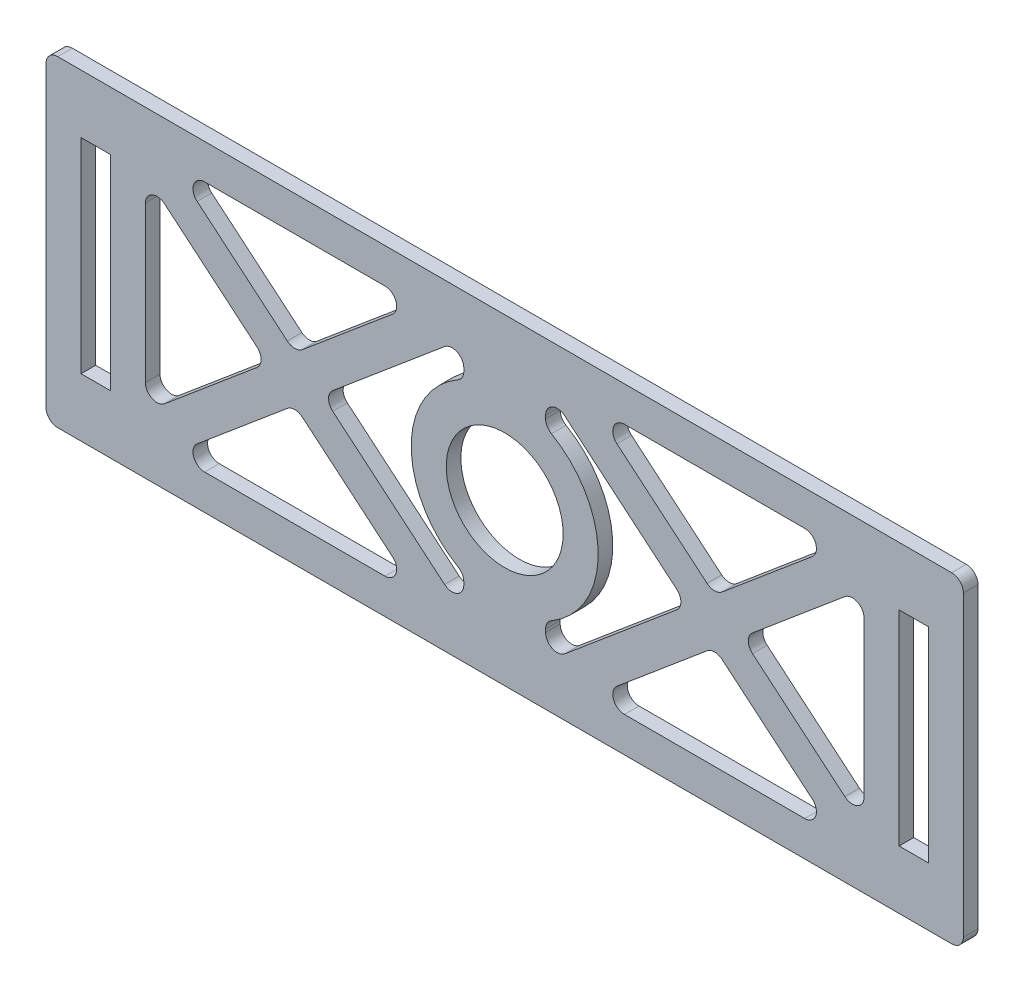
SolidWorks part; units mm, degrees
ref_plane "Front Plane" through (0, 0, 0) normal (0, 0, 1) x (1, 0, 0)
ref_plane "Top Plane" through (0, 0, 0) normal (0, 1, 0) x (1, 0, 0)
ref_plane "Right Plane" through (0, 0, 0) normal (1, 0, 0) x (0, 0, -1)
sketch "Sketch1" plane through (0, 0, 0) normal (0, 0, 1) x (1, 0, 0)
  line L0 (88.9, -28.575) -> (88.9, -73.025) construction
  line L1 (-99.695, -15.875) -> (99.695, -15.875)
  line L2 (-99.695, -15.875) -> (-99.695, -85.725)
  line L3 (-99.695, -85.725) -> (99.695, -85.725)
  line L4 (99.695, -15.875) -> (99.695, -85.725)
  line L5 (85.725, -28.575) -> (92.075, -28.575)
  line L6 (85.725, -28.575) -> (85.725, -73.025)
  line L7 (85.725, -73.025) -> (92.075, -73.025)
  line L8 (92.075, -28.575) -> (92.075, -73.025)
  line L9 (8.89, -23.495) -> (8.89, -24.9079)
  line L10 (8.89, -78.105) -> (78.105, -78.105)
  line L11 (78.105, -78.105) -> (78.105, -23.495)
  line L12 (78.105, -23.495) -> (8.89, -23.495)
  line L13 (8.89, -78.105) -> (8.89, -76.6921)
  line L14 (8.89, -24.9079) -> (72.1834, -78.105)
  line L15 (78.105, -78.105) -> (13.1305, -23.495)
  line L16 (78.105, -73.128) -> (19.0521, -23.495)
  line L17 (27.0702, -40.1881) -> (31.973, -34.3548) construction
  line L18 (2.2061, -50.8) -> (31.6359, -50.8) construction
  line L19 (78.105, -28.472) -> (19.0521, -78.105)
  line L20 (8.89, -76.6921) -> (72.1834, -23.495)
  line L21 (8.89, -32.5279) -> (8.89, -24.9079)
  line L22 (8.89, -76.6921) -> (8.89, -69.0721)
  circle A0 centre (0, -50.8) radius 12.7
  arc A1 (8.89, -24.9079) -> (8.89, -76.6921) centre (0, -50.8) cw
  arc A2 (8.89, -32.5279) -> (8.89, -69.0721) centre (0, -50.8) cw
  point P2 (0, -50.8)
  point P11 (85.725, -50.8)
  point P14 (0, -15.875)
  point P28 (29.5216, -37.2714)
  point P33 (78.105, -50.8)
  dimension "D1" = 25.4
  dimension "D2" = 44.45
  dimension "D3" = 6.35
  dimension "D4" = 88.9
  dimension "D5" = 12.7
  dimension "D6" = 7.62
  dimension "D7" = 12.7
  dimension "D9" = 7.62
  dimension "D12" = 7.62
  dimension "D13" = 50.8
  dimension "D8" = 7.62
  dimension "D10" = 8.89
  dimension "D11" = 7.62
  dimension "D14" = 7.62
extrude "Boss-Extrude1" add sketch "Sketch1" along normal mid plane 3.175 contours L4 L1 L2 L3 A1 L14 L9 L12 L11 L10 L13 L20 A0 L5 L8 L7 L6 | L14 L19 L10 | L20 A1 L13 L10 L19 L14 | L20 L14 L19 | L20 L19 L16 | L19 L14 L10 | L16 L19 L11 | L11 L19 L16 | L20 L16 L19 L11 L12 | L16 L20 L12 | L20 L16 L12 | L9 A1 L14 L20 | L14 A1 L20 | A1 L20 | A1 L14 | L21 A2 L22 L20 A1 L14 region at (-19.201, -50.8, 0) region at (27.442, -37.7533, 0) region at (16.9069, -30.6844, 0) region at (16.0795, -31.6688, 0) region at (30.0753, -35.2921, 0) region at (30.8144, -50.8, 0) region at (45.6178, -30.9377, 0) region at (47.0982, -49.5558, 0) region at (44.1374, -52.0442, 0) region at (28.8113, -65.1265, 0) region at (16.9069, -70.9156, 0) region at (62.6146, -36.5144, 0) region at (64.069, -63.8632, 0) region at (61.1603, -66.3079, 0) region at (45.6178, -70.6623, 0) region at (69.2498, -50.8, 0)
extrude "Cut-Extrude1" cut sketch "Sketch1<3>" against normal mid plane 6.35 contours L14 A1 L20 | L16 L20 L12 | L11 L19 L16 | L14 L19 L10 | L8 L5 L6 L7 | L21 A2 L22 L20 A1 L14 region at (88.9, -50.8, 0) region at (16.0795, -31.6688, 0) region at (30.8144, -50.8, 0) region at (45.6178, -30.9377, 0) region at (45.6178, -70.6623, 0) region at (69.2498, -50.8, 0)
sketch "Sketch1<3>" plane through (0, 0, 0) normal (0, 0, 1) x (1, 0, 0) same geometry as "Sketch1"
mirror "Mirror1" about plane through (0, 0, 0) normal (1, 0, 0) of "Cut-Extrude1"
fillet "Fillet1" radius 2.54 32 edges at (51.5394, -50.8, 0) (78.105, -28.472, 0) (78.105, -73.128, 0) (39.6962, -50.8, 0) (72.1834, -78.105, 0) (19.0521, -78.105, 0) (45.6178, -55.777, 0) (19.0521, -23.495, 0) (72.1834, -23.495, 0) (45.6178, -45.823, 0) (99.695, -85.725, 0) (99.695, -15.875, 0) (-99.695, -85.725, 0) (-99.695, -15.875, 0) (-78.105, -28.472, 0) (-51.5394, -50.8, 0) (-78.105, -73.128, 0) (-39.6962, -50.8, 0) (-72.1834, -78.105, 0) (-45.6178, -55.777, 0) (-19.0521, -78.105, 0) (-72.1834, -23.495, 0) (-45.6178, -45.823, 0) (-19.0521, -23.495, 0) (-8.89, -32.5279, 0) (-8.89, -76.6921, 0) (-8.89, -24.9079, 0) (-8.89, -69.0721, 0) (8.89, -76.6921, 0) (8.89, -69.0721, 0) (8.89, -32.5279, 0) (8.89, -24.9079, 0)
equation "\"D5@Sketch1\"=\"D7@Sketch1\""
